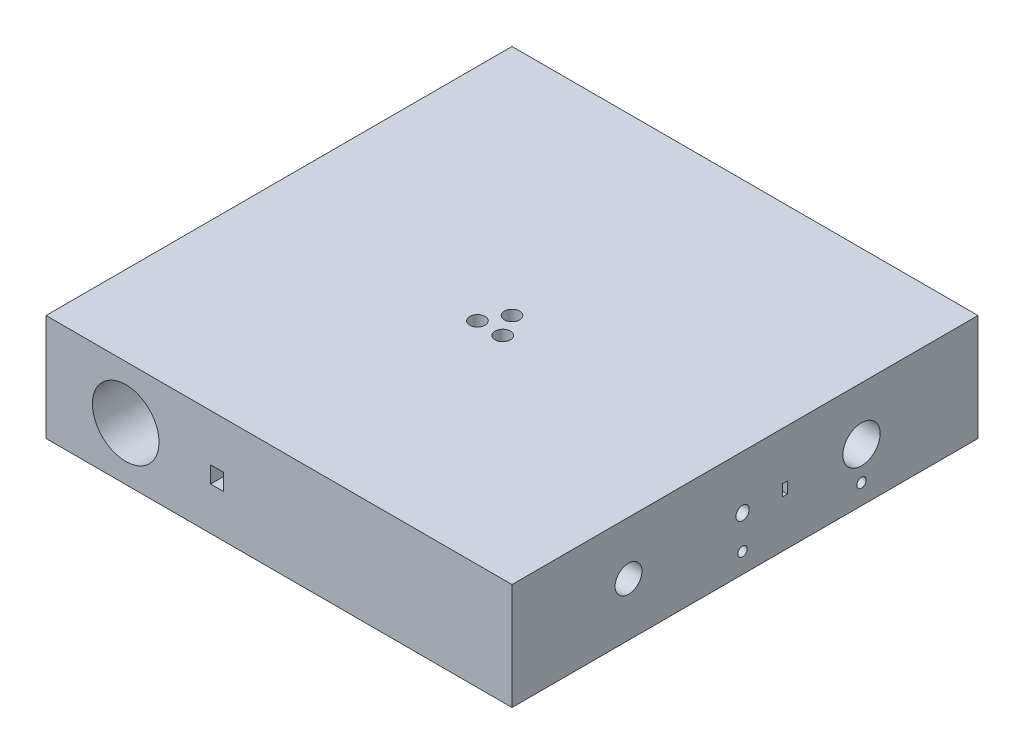
SolidWorks part; units mm, degrees
ref_plane "Front Plane" through (0, 0, 0) normal (0, 0, 1) x (1, 0, 0)
ref_plane "Top Plane" through (0, 0, 0) normal (0, 1, 0) x (1, 0, 0)
ref_plane "Right Plane" through (0, 0, 0) normal (1, 0, 0) x (0, 0, -1)
sketch "Sketch1" plane through (0, 0, 0) normal (0, 1, 0) x (1, 0, 0)
  line L1 (-175, 175) -> (175, 175)
  line L2 (-175, 175) -> (-175, -175)
  line L3 (-175, -175) -> (175, -175)
  line L4 (175, 175) -> (175, -175)
  line L5 (-175, 175) -> (175, -175) construction
  line L6 (-175, -175) -> (175, 175) construction
  point P0 (0, 0)
  dimension "D1" = 350
  dimension "D2" = 350
extrude "Boss-Extrude1" add sketch "Sketch1" along normal blind 80
sketch "Sketch2" plane through (0, 80, 0) normal (0, 1, 0) x (1, 0, 0)
  line L0 (0, 0) -> (0, 175)
  line L1 (175, 175) -> (-175, 175) construction
  line L2 (175, -175) -> (175, 175) construction
  line L3 (-175, 175) -> (-175, -175) construction
  circle A0 centre (0, 0) radius 5.75
  circle A1 centre (9.5, -16.4545) radius 5.75
  circle A2 centre (-9.5, -16.4545) radius 5.75
  point P7 (175, 0)
  dimension "D1" = 11.5
  dimension "D5" = 11.5
  dimension "D6" = 11.5
  dimension "D9" = 165.5
  dimension "D2" = 175
  dimension "D3" = 175
  dimension "D4" = 19
  dimension "D7" = 19
  dimension "D8" = 165.5
extrude "Cut-Extrude1" cut sketch "Sketch2" against normal through all contours A0 region at (-3.9509, 80, 3.9509)
extrude "Cut-Extrude2" cut sketch "Sketch2<4>" against normal through all contours A1 region at (9.5, 80, 16.4545)
sketch "Sketch2<4>" plane through (0, 80, 0) normal (0, 1, 0) x (1, 0, 0) same geometry as "Sketch2"
extrude "Cut-Extrude3" cut sketch "Sketch2<5>" against normal through all contours A2 region at (-9.5, 80, 16.4545)
sketch "Sketch2<5>" plane through (0, 80, 0) normal (0, 1, 0) x (1, 0, 0) same geometry as "Sketch2"
sketch "Sketch3" plane through (-175, 0, 0) normal (-1, 0, 0) x (0, 0, 1)
  line L0 (-175, 80) -> (-175, 0) construction
  line L1 (-28.15, 35.4316) -> (-31.85, 35.4316)
  line L2 (-28.15, 35.4316) -> (-28.15, 43.9316)
  line L3 (-28.15, 43.9316) -> (-31.85, 43.9316)
  line L4 (-31.85, 35.4316) -> (-31.85, 43.9316)
  line L5 (-28.15, 35.4316) -> (-31.85, 43.9316) construction
  line L6 (-28.15, 43.9316) -> (-31.85, 35.4316) construction
  point P0 (-30, 39.6816)
  point P7 (-175, 40)
  dimension "D1" = 8.5
  dimension "D2" = 3.7
  dimension "D3" = 145
extrude "Cut-Extrude4" cut sketch "Sketch3" against normal through all
sketch "Sketch4" plane through (-175, 0, 0) normal (-1, 0, 0) x (0, 0, 1)
  line L0 (175, 80) -> (175, 0) construction
  line L3 (-175, 0) -> (175, 0) construction
  circle A0 centre (87.5, 40) radius 10.1
  dimension "D1" = 20.2
  dimension "D2" = 87.5
  dimension "D3" = 40
extrude "Cut-Extrude5" cut sketch "Sketch4" against normal through all
sketch "Sketch6" plane through (-175, 0, 0) normal (-1, 0, 0) x (0, 0, 1)
  line L0 (-28.15, 35.4316) -> (-28.15, 43.9316) construction
  line L1 (-175, 0) -> (175, 0) construction
  circle A0 centre (1.85, 15) radius 3.555
  point P5 (-28.15, 39.6816)
  dimension "D1" = 7.11
  dimension "D2" = 30
  dimension "D3" = 15
extrude "Cut-Extrude7" cut sketch "Sketch6" against normal through all and the other way blind 10
sketch "Sketch7" plane through (-175, 0, 0) normal (-1, 0, 0) x (0, 0, 1)
  line L0 (-175, 80) -> (-175, 0) construction
  line L1 (-175, 0) -> (175, 0) construction
  circle A0 centre (-87.5, 15) radius 3.555
  dimension "D1" = 7.11
  dimension "D2" = 87.5
  dimension "D3" = 15
extrude "Cut-Extrude8" cut sketch "Sketch7" against normal through all
sketch "Sketch9" plane through (-175, 0, 0) normal (-1, 0, 0) x (0, 0, 1)
  line L0 (-175, 80) -> (-175, 0) construction
  line L1 (-175, 0) -> (175, 0) construction
  circle A0 centre (-87.5, 40) radius 14
  dimension "D1" = 28
  dimension "D2" = 87.5
  dimension "D3" = 40
extrude "Cut-Extrude10" cut sketch "Sketch9" against normal through all
sketch "Sketch11" plane through (-175, 0, 0) normal (-1, 0, 0) x (0, 0, 1)
  line L3 (-28.15, 35.4316) -> (-28.15, 43.9316) construction
  line L4 (-175, 0) -> (175, 0) construction
  circle A0 centre (1.85, 40) radius 5.025
  dimension "D1" = 10.05
  dimension "D2" = 30
  dimension "D3" = 40
extrude "Cut-Extrude12" cut sketch "Sketch11" against normal through all
sketch "Sketch13" plane through (0, 0, -175) normal (0, 0, -1) x (-1, 0, 0)
  line L0 (-175, 0) -> (175, 0) construction
  circle A0 centre (115.112, 40) radius 25
  dimension "D1" = 50
  dimension "D2" = 40
extrude "Cut-Extrude14" cut sketch "Sketch13" against normal through all
sketch "Sketch14" plane through (0, 0, -175) normal (0, 0, -1) x (-1, 0, 0)
  line L1 (51.3298, 32.1941) -> (41.6298, 32.1941)
  line L2 (51.3298, 32.1941) -> (51.3298, 44.6941)
  line L3 (51.3298, 44.6941) -> (41.6298, 44.6941)
  line L4 (41.6298, 32.1941) -> (41.6298, 44.6941)
  line L5 (51.3298, 32.1941) -> (41.6298, 44.6941) construction
  line L6 (51.3298, 44.6941) -> (41.6298, 32.1941) construction
  point P0 (46.4798, 38.4441)
  dimension "D1" = 9.7
  dimension "D2" = 12.5
extrude "Cut-Extrude18" cut sketch "Sketch14" against normal through all
